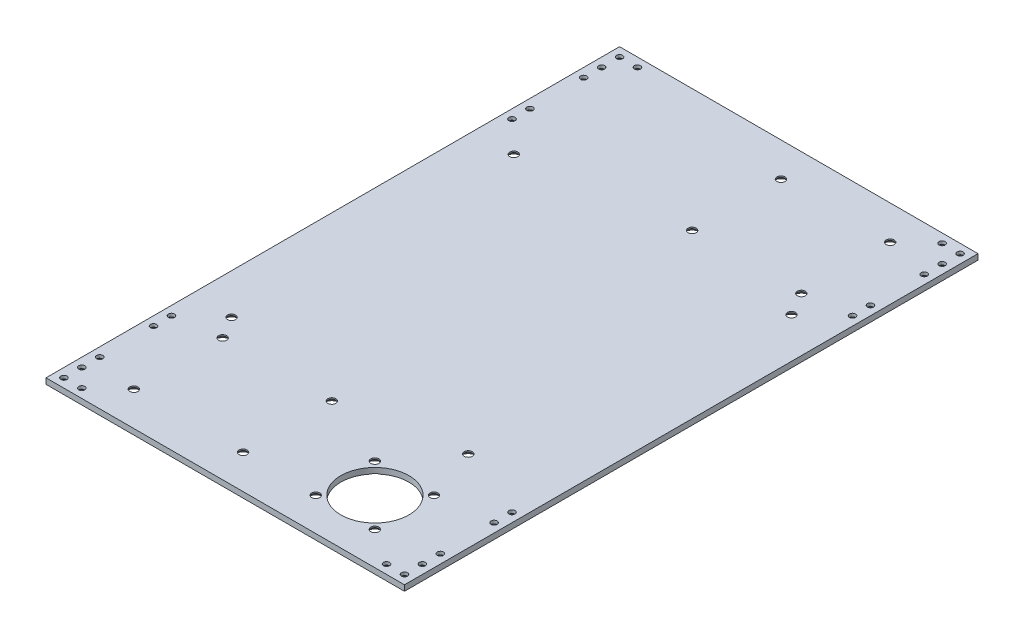
SolidWorks part; units mm, degrees
material "Garolite (G-10/FR4)"
ref_plane "Front Plane" through (0, 0, 0) normal (0, 0, 1) x (1, 0, 0)
ref_plane "Top Plane" through (0, 0, 0) normal (0, 1, 0) x (1, 0, 0)
ref_plane "Right Plane" through (0, 0, 0) normal (1, 0, 0) x (0, 0, -1)
sketch "Sketch1" plane through (0, 0, 0) normal (0, 1, 0) x (1, 0, 0)
  line L0 (0, -160) -> (0, 160) construction
  line L1 (-100, 160) -> (100, 160)
  line L2 (-100, 160) -> (-100, -160)
  line L3 (-100, -160) -> (100, -160)
  line L4 (100, 160) -> (100, -160)
  line L5 (100, 0) -> (-100, 0) construction
  dimension "D1" = 320
  dimension "D2" = 200
extrude "Boss-Extrude1" add sketch "Sketch1" along normal blind 3.175
hole_wizard "CSK for M3 Flat Head Machine Screw1" positions "Sketch3" profile "Sketch2" countersink size "M3" standard "Ansi Metric" end condition through all
sketch "Sketch3" plane through (0, 0, 0) normal (0, -1, 0) x (1, 0, 0)
  line L0 (-100, 155) -> (-85, 155) construction
  line L1 (-100, -160) -> (-100, 160) construction
  line L3 (-95, 95) -> (-95, 160) construction
  line L4 (-100, 160) -> (100, 160) construction
  line L6 (-100, -160) -> (-100, 160) construction
  point P0 (-95, 155)
  point P1 (-85, 155)
  point P3 (-95, 145)
  point P5 (-95, 135)
  point P40 (-95, 105)
  point P42 (-95, 95)
  dimension "D1" = 10
  dimension "D2" = 10
  dimension "D3" = 10
  dimension "D4" = 5
  dimension "D5" = 5
  dimension "D6" = 10
  dimension "D7" = 30
sketch "Sketch2" plane through (-95, 0, 155) normal (1, 0, 0) x (0, 0, -1)
  line L0 (0, 0) -> (0, 3.175)
  line L1 (0, 3.175) -> (1.7, 3.175)
  line L2 (1.7, 3.175) -> (1.7, 1.45)
  line L3 (1.7, 1.45) -> (3.15, 0)
  line L5 (3.15, 0) -> (0, 0)
  line L6 (-1.7, 1.45) -> (-3.15, 0) construction
  line L11 (0, -6.35) -> (0, 107.95) construction
  dimension "Thru Hole Dia." = 3.4
  dimension "Thru Hole Depth" = 3.175
  dimension "Near C'Sink Dia." = 6.3
  dimension "Near C'Sink Angle" = 90
mirror "Mirror1" about plane through (0, 0, 0) normal (1, 0, 0) of "CSK for M3 Flat Head Machine Screw1"
mirror "Mirror2" about plane through (0, 0, 0) normal (0, 0, 1) of "Mirror1"
hole_wizard "CSK for M4 Flat Head Machine Screw1" positions "Sketch7" profile "Sketch6" countersink size "M4" standard "Ansi Metric" end condition through all
sketch "Sketch7" plane through (0, 0, 0) normal (0, -1, 0) x (1, 0, 0)
  line L1 (65, 108.5) -> (32, 108.5)
  line L2 (65, 108.5) -> (65, 141.5)
  line L3 (65, 141.5) -> (32, 141.5)
  line L4 (32, 108.5) -> (32, 141.5)
  line L6 (-9.04, 91.47) -> (-70, 91.47)
  line L7 (-9.04, 91.47) -> (-9.04, 141)
  line L8 (-9.04, 141) -> (-70, 141)
  line L9 (-70, 91.47) -> (-70, 141)
  line L11 (9.04, -141) -> (70, -141)
  line L12 (9.04, -141) -> (9.04, -91.47)
  line L13 (9.04, -91.47) -> (70, -91.47)
  line L14 (70, -141) -> (70, -91.47)
  line L15 (-100, 160) -> (100, 160) construction
  line L16 (100, 160) -> (100, -160) construction
  line L17 (-100, -160) -> (-100, 160) construction
  line L18 (100, -160) -> (-100, -160) construction
  line L20 (-77.47, -78.48) -> (77.47, -78.48)
  line L21 (-77.47, -78.48) -> (-77.47, 79)
  line L22 (-77.47, 79) -> (77.47, 79)
  line L23 (77.47, -78.48) -> (77.47, 79)
  line L25 (-77.47, 0.26) -> (-100, 0.26) construction
  line L27 (77.47, 0.26) -> (100, 0.26) construction
  line L29 (100, 160) -> (100, -160) construction
  line L30 (-100, -160) -> (-100, 160) construction
  line L31 (-100, 160) -> (100, 160) construction
  point P0 (-9.04, 91.47)
  point P1 (32, 141.5)
  point P3 (32, 108.5)
  point P5 (65, 108.5)
  point P7 (-70, 141)
  point P9 (-70, 91.47)
  point P11 (-9.04, 141)
  point P13 (65, 141.5)
  point P15 (70, -141)
  point P17 (9.04, -141)
  point P19 (9.04, -91.47)
  point P21 (70, -91.47)
  point P375 (54.61, 79)
  point P377 (77.47, -78.48)
  point P379 (-77.47, -78.48)
  point P381 (-77.47, 79)
  dimension "D1" = 33
  dimension "D2" = 18.5
  dimension "D3" = 35
  dimension "D4" = 60.96
  dimension "D5" = 49.53
  dimension "D6" = 19
  dimension "D7" = 30
  dimension "D8" = 19
  dimension "D9" = 30
  dimension "D10" = 154.94
  dimension "D11" = 22.86
  dimension "D12" = 157.48
  dimension "D13" = 81
sketch "Sketch6" plane through (-9.04, 0, 91.47) normal (1, 0, 0) x (0, 0, -1)
  line L0 (0, 0) -> (0, 3.175)
  line L1 (0, 3.175) -> (2.25, 3.175)
  line L2 (2.25, 3.175) -> (2.25, 2.45)
  line L3 (2.25, 2.45) -> (4.7, 0)
  line L5 (4.7, 0) -> (0, 0)
  line L6 (-2.25, 2.45) -> (-4.7, 0) construction
  line L11 (0, -6.35) -> (0, 107.95) construction
  dimension "Thru Hole Dia." = 4.5
  dimension "Thru Hole Depth" = 3.175
  dimension "Near C'Sink Dia." = 9.4
  dimension "Near C'Sink Angle" = 90
sketch "Sketch8" plane through (0, 3.175, 0) normal (0, 1, 0) x (1, 0, 0)
  line L0 (65, -141.5) -> (32, -108.5) construction
  line L1 (32, -141.5) -> (65, -108.5) construction
  circle A0 centre (48.5, -125) radius 19
  dimension "D1" = 38
extrude "Cut-Extrude1" cut sketch "Sketch8" against normal through all
